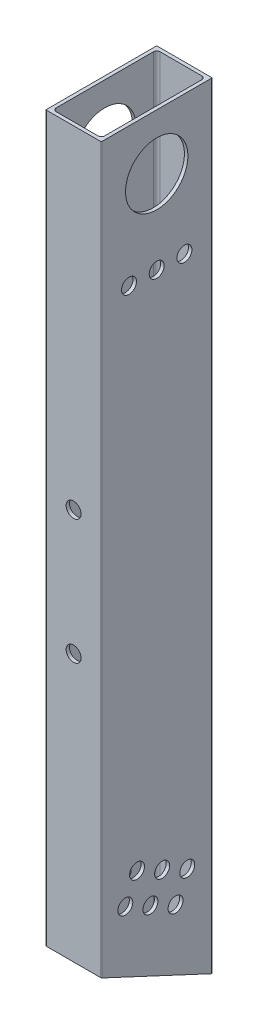
SolidWorks part; units mm, degrees
ref_plane "Front Plane" through (0, 0, 0) normal (0, 0, 1) x (1, 0, 0)
ref_plane "Top Plane" through (0, 0, 0) normal (0, 1, 0) x (1, 0, 0)
ref_plane "Right Plane" through (0, 0, 0) normal (1, 0, 0) x (0, 0, -1)
sketch "Sketch1" plane through (0, 0, 0) normal (0, 1, 0) x (1, 0, 0)
  line L0 (-9.5885, 23.8125) -> (9.5885, 23.8125)
  line L1 (-12.446, -25.4) -> (12.446, -25.4)
  line L2 (-12.7, -25.146) -> (-12.7, 25.146)
  line L3 (-12.446, 25.4) -> (12.446, 25.4)
  line L4 (12.7, -25.146) -> (12.7, 25.146)
  line L5 (-12.7, -25.4) -> (12.7, 25.4) construction
  line L6 (-12.7, 25.4) -> (12.7, -25.4) construction
  line L7 (11.1125, -22.2885) -> (11.1125, 22.2885)
  line L8 (-9.5885, -23.8125) -> (9.5885, -23.8125)
  line L9 (-11.1125, -22.2885) -> (-11.1125, 22.2885)
  line L10 (-11.1125, -23.8125) -> (-11.1125, 23.8125) construction
  line L11 (-11.1125, -23.8125) -> (11.1125, -23.8125) construction
  line L12 (11.1125, -23.8125) -> (11.1125, 23.8125) construction
  line L13 (-11.1125, 23.8125) -> (11.1125, 23.8125) construction
  arc A0 (-12.446, -25.4) -> (-12.7, -25.146) centre (-12.446, -25.146) cw
  arc A1 (12.446, -25.4) -> (12.7, -25.146) centre (12.446, -25.146) ccw
  arc A2 (12.446, 25.4) -> (12.7, 25.146) centre (12.446, 25.146) cw
  arc A3 (-12.7, 25.146) -> (-12.446, 25.4) centre (-12.446, 25.146) cw
  arc A8 (-11.1125, -22.2885) -> (-9.5885, -23.8125) centre (-9.5885, -22.2885) ccw
  arc A9 (-11.1125, -23.8125) -> (-11.1125, -23.8125) centre (-11.1125, -23.8125) cw construction
  arc A10 (9.5885, -23.8125) -> (11.1125, -22.2885) centre (9.5885, -22.2885) ccw
  arc A11 (11.1125, -23.8125) -> (11.1125, -23.8125) centre (11.1125, -23.8125) ccw construction
  arc A12 (11.1125, 22.2885) -> (9.5885, 23.8125) centre (9.5885, 22.2885) ccw
  arc A13 (11.1125, 23.8125) -> (11.1125, 23.8125) centre (11.1125, 23.8125) cw construction
  arc A14 (-11.1125, 22.2885) -> (-9.5885, 23.8125) centre (-9.5885, 22.2885) cw
  arc A15 (-11.1125, 23.8125) -> (-11.1125, 23.8125) centre (-11.1125, 23.8125) cw construction
  point P0 (0, 0)
  dimension "D3" = 0.254
  dimension "D5" = 1.524
  dimension "D1" = 50.8
  dimension "D2" = 25.4
  dimension "D4" = 1.5875
extrude "Boss-Extrude1" add sketch "Sketch1" along normal blind 355.6
sketch "Sketch2" plane through (-12.7, 0, 0) normal (-1, 0, 0) x (0, 0, 1)
  line L1 (0, 355.6) -> (0, 0) construction
  line L2 (-25.146, 355.6) -> (25.146, 355.6) construction
  line L3 (13.97, 0) -> (-13.97, 0) construction
  line L4 (-25.4, 0) -> (25.4, 23.6884)
  line L5 (-25.4, 355.6) -> (-25.4, 0) construction
  line L6 (25.4, 355.6) -> (25.4, 0) construction
  line L7 (25.4, 23.6884) -> (25.4, 0)
  line L8 (-8.6326, 35.8446) -> (0, 39.87) construction
  line L9 (25.4, 0) -> (-25.4, 0)
  line L10 (-12.7, 292.1) -> (12.7, 292.1) construction
  circle A0 centre (-8.6326, 35.8446) radius 3.429
  circle A1 centre (0, 330.2) radius 14.2875
  circle A2 centre (0, 292.1) radius 3.429
  circle A3 centre (12.7, 292.1) radius 3.429
  circle A4 centre (-12.7, 292.1) radius 3.429
  circle A5 centre (2.8775, 41.2118) radius 3.429
  circle A6 centre (14.3876, 46.5791) radius 3.429
  circle A7 centre (-2.4897, 52.7219) radius 3.429
  circle A8 centre (9.0204, 58.0892) radius 3.429
  circle A9 centre (-13.9998, 47.3547) radius 3.429
  point P25 (0, 292.1)
  dimension "D1" = 6.858
  dimension "D2" = 25.4
  dimension "D4" = 25.4
  dimension "D5" = 28.575
  dimension "D6" = 38.1
  dimension "D9" = 3
  dimension "D10" = 2
  dimension "D7" = 12.7
  dimension "D11" = 12.7
  dimension "D3" = 65
  dimension "D8" = 25.4
  dimension "D12" = 9.525
extrude "Cut-Extrude1" cut sketch "Sketch2" against normal through all
sketch "Sketch3" plane through (0, 0, 0) normal (0, 0, 1) x (1, 0, 0)
  line L0 (0, -27.94) -> (0, 27.94) construction
  line L1 (-12.446, 355.6) -> (12.446, 355.6) construction
  circle A0 centre (0, 203.2) radius 3.429
  circle A1 centre (0, 146.05) radius 3.429
  circle A2 centre (0, 203.2) radius 9.525
  circle A3 centre (0, 146.05) radius 9.525
  dimension "D1" = 6.858
  dimension "D2" = 57.15
  dimension "D3" = 152.4
  dimension "D4" = 19.05
extrude "Cut-Extrude2" cut sketch "Sketch3" along normal through all contours A0 | A1
extrude "Cut-Extrude3" cut sketch "Sketch3<3>" against normal through all contours A2 | A3
sketch "Sketch3<3>" plane through (0, 0, 0) normal (0, 0, 1) x (1, 0, 0) same geometry as "Sketch3"
